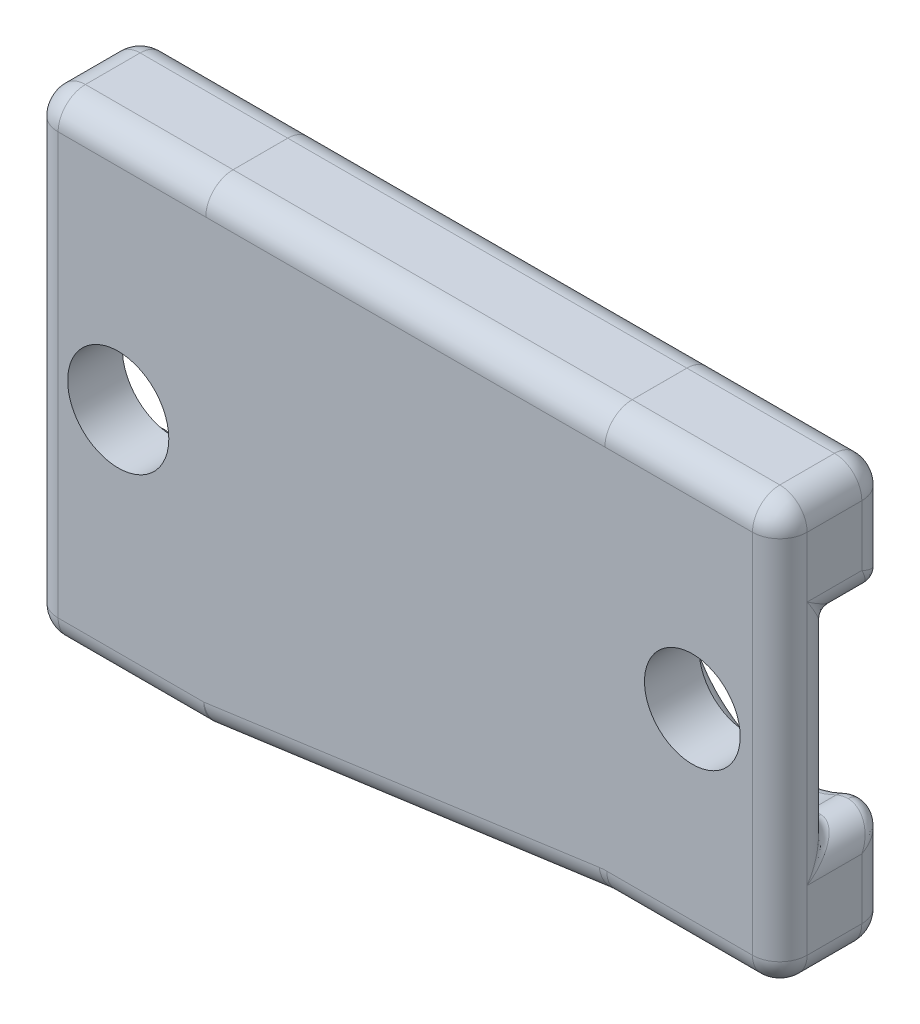
SolidWorks part; units mm, degrees
ref_plane "Front Plane" through (0, 0, 0) normal (0, 0, 1) x (1, 0, 0)
ref_plane "Top Plane" through (0, 0, 0) normal (0, 1, 0) x (1, 0, 0)
ref_plane "Right Plane" through (0, 0, 0) normal (1, 0, 0) x (0, 0, -1)
sketch "Sketch1" plane through (0, 0, 0) normal (0, 0, 1) x (1, 0, 0)
  line L0 (-107.8, -56.6646) -> (-93.2, -56.6493)
  line L1 (-107.8, -74.0646) -> (-93.2, -72.0493)
  line L8 (-86.8, -72.0493) -> (-86.8, -56.6493)
  line L9 (-86.8, -56.6493) -> (-93.2, -56.6493)
  line L11 (-93.2, -72.0493) -> (-86.8, -72.0493)
  line L12 (-114.2, -74.0646) -> (-107.8, -74.0646)
  line L14 (-107.8, -56.6646) -> (-114.2, -56.6646)
  line L15 (-114.2, -56.6646) -> (-114.2, -74.0646)
  circle A0 centre (-111, -65.3646) radius 1.85
  circle A1 centre (-90, -64.3493) radius 1.75
  dimension "D2" = 3.5
  dimension "D1" = 6.4
extrude "Boss-Extrude1" add sketch "Sketch1" along normal blind 4
sketch "Sketch2" plane through (0, 0, 0) normal (0, 0, 1) x (1, 0, 0)
  circle A0 centre (-111, -65.3646) radius 4
  circle A1 centre (-90, -64.3493) radius 4
  dimension "D1" = 8
  dimension "D2" = 8
extrude "Cut-Extrude1" cut sketch "Sketch2" along normal blind 2
fillet "Fillet1" radius 1 32 edges at (-90, -56.6493, 4) (-90, -56.6493, 0) (-93.2, -56.6493, 2) (-100.5, -56.657, 4) (-100.5, -56.657, 0) (-114.2, -62.9646, 1) (-114.2, -65.3646, 4) (-114.2, -70.9146, 0) (-114.2, -59.8146, 0) (-114.2, -67.7646, 1) (-114.2, -65.3646, 2) (-114.2, -74.0646, 2) (-111, -74.0646, 4) (-111, -74.0646, 0) (-107.8, -74.0646, 2) (-100.5, -73.057, 4) (-100.5, -73.057, 0) (-93.2, -72.0493, 2) (-90, -72.0493, 4) (-90, -72.0493, 0) (-86.8, -66.7493, 1) (-86.8, -64.3493, 4) (-86.8, -56.6493, 2) (-86.8, -59.2993, 0) (-86.8, -69.3993, 0) (-86.8, -72.0493, 2) (-86.8, -61.9493, 1) (-86.8, -64.3493, 2) (-107.8, -56.6646, 2) (-111, -56.6646, 4) (-114.2, -56.6646, 2) (-111, -56.6646, 0)
fillet "Fillet2" radius 0.5 20 edges at (-87.0929, -60.5665, 0.2929) (-88.0258, -60.8335, 0) (-87.0929, -68.1322, 0.2929) (-88.0258, -67.8652, 0) (-87.0929, -60.5665, 2.2929) (-88.0258, -60.8335, 2) (-87.0929, -68.1322, 2.2929) (-88.0258, -67.8652, 2) (-113.9071, -69.1474, 0.2929) (-112.9742, -68.8804, 0) (-113.9071, -61.5817, 0.2929) (-112.9742, -61.8487, 0) (-113.9071, -69.1474, 2.2929) (-112.9742, -68.8804, 2) (-113.9071, -61.5817, 2.2929) (-112.9742, -61.8487, 2) (-94, -64.3493, 0) (-94, -64.3493, 2) (-107, -65.3646, 0) (-107, -65.3646, 2)
